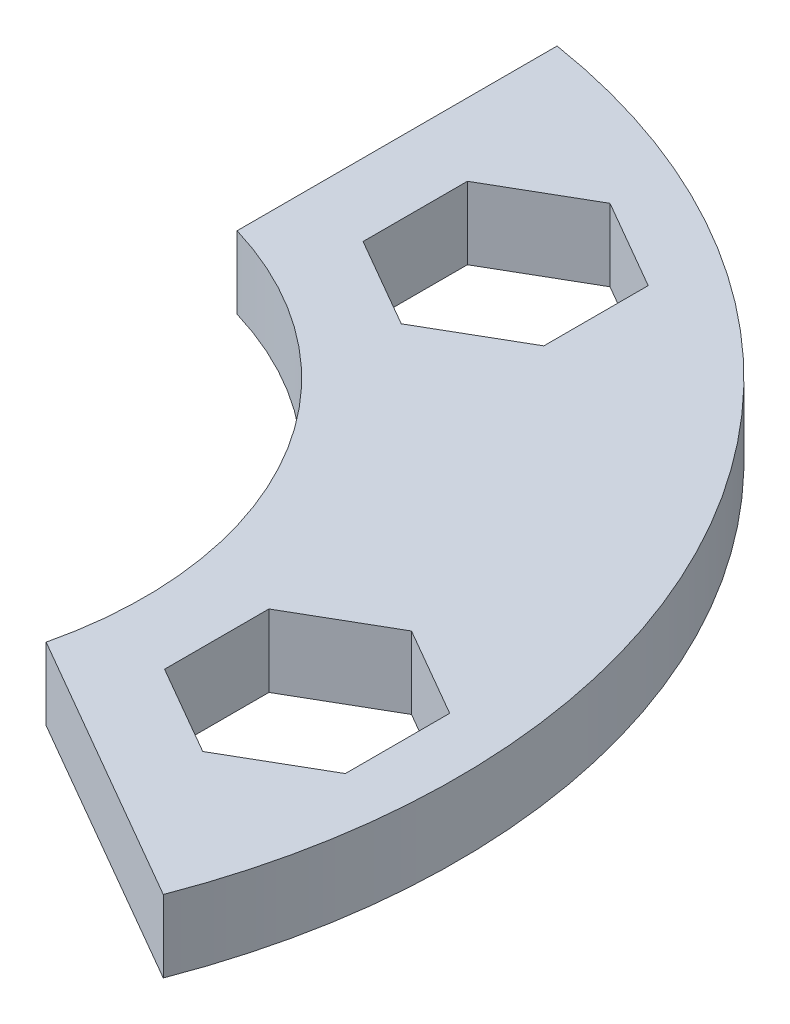
SolidWorks part; units mm, degrees
material "Balsa"
ref_plane "Front Plane" through (0, 0, 0) normal (0, 0, 1) x (1, 0, 0)
ref_plane "Top Plane" through (0, 0, 0) normal (0, 1, 0) x (1, 0, 0)
ref_plane "Right Plane" through (0, 0, 0) normal (1, 0, 0) x (0, 0, -1)
sketch "Sketch1" plane through (0, 0, 0) normal (0, 1, 0) x (1, 0, 0)
  line L0 (-38.3, 0) -> (38.3, 0) construction
  line L1 (0, 38.3) -> (0, -38.3) construction
  line L2 (10, -28.8675) -> (15, -31.7543)
  line L3 (30, 5.7735) -> (25, 2.8868)
  line L4 (25, 2.8868) -> (25, -2.8868)
  line L5 (25, -2.8868) -> (30, -5.7735)
  line L6 (30, -5.7735) -> (35, -2.8868)
  line L7 (35, -2.8868) -> (35, 2.8868)
  line L8 (35, 2.8868) -> (30, 5.7735)
  line L9 (10, -23.094) -> (10, -28.8675)
  line L10 (15, -20.2073) -> (10, -23.094)
  line L11 (20, -23.094) -> (15, -20.2073)
  line L12 (20, -28.8675) -> (20, -23.094)
  line L13 (15, -31.7543) -> (20, -28.8675)
  line L14 (-20, -23.094) -> (-20, -28.8675)
  line L15 (-15, -20.2073) -> (-20, -23.094)
  line L16 (-10, -23.094) -> (-15, -20.2073)
  line L17 (-10, -28.8675) -> (-10, -23.094)
  line L18 (-15, -31.7543) -> (-10, -28.8675)
  line L19 (-20, -28.8675) -> (-15, -31.7543)
  line L20 (-30, 5.7735) -> (-35, 2.8868)
  line L21 (-25, 2.8868) -> (-30, 5.7735)
  line L22 (-25, -2.8868) -> (-25, 2.8868)
  line L23 (-30, -5.7735) -> (-25, -2.8868)
  line L24 (-35, -2.8868) -> (-30, -5.7735)
  line L25 (-35, 2.8868) -> (-35, -2.8868)
  line L26 (-10, 28.8675) -> (-15, 31.7543)
  line L27 (-10, 23.094) -> (-10, 28.8675)
  line L28 (-15, 20.2073) -> (-10, 23.094)
  line L29 (-20, 23.094) -> (-15, 20.2073)
  line L30 (-20, 28.8675) -> (-20, 23.094)
  line L31 (-15, 31.7543) -> (-20, 28.8675)
  line L32 (20, 23.094) -> (20, 28.8675)
  line L33 (15, 20.2073) -> (20, 23.094)
  line L34 (10, 23.094) -> (15, 20.2073)
  line L35 (10, 28.8675) -> (10, 23.094)
  line L36 (15, 31.7543) -> (10, 28.8675)
  line L37 (20, 28.8675) -> (15, 31.7543)
  circle A0 centre (0, 0) radius 38.3
  circle A1 centre (30, 0) radius 5 construction
  circle A2 centre (0, 0) radius 21
  circle A3 centre (15, -25.9808) radius 5 construction
  circle A4 centre (-15, -25.9808) radius 5 construction
  circle A5 centre (-30, 0) radius 5 construction
  circle A6 centre (-15, 25.9808) radius 5 construction
  circle A7 centre (15, 25.9808) radius 5 construction
  point P23 (0, 0)
  point P60 (0, 0)
  dimension "D1" = 42
  dimension "D2" = 76.6
  dimension "D3" = 10
  dimension "D4" = 30
  dimension "D5" = 6
extrude "Boss-Extrude1" add sketch "Sketch1" along normal blind 4
sketch "Sketch2" plane through (0, 4, 0) normal (0, 1, 0) x (1, 0, 0)
  line L0 (0, 0) -> (0, 45.284) construction
  line L1 (0, 0) -> (52.3716, -30.2368) construction
  line L2 (6, 50.2763) -> (6, 14.2975)
  line L3 (15.382, -1.9526) -> (46.5406, -19.942)
  arc A0 (15.382, -1.9526) -> (6, 14.2975) centre (0, 0) ccw
  arc A2 (6, 50.2763) -> (46.5406, -19.942) centre (0, 0) ccw
  dimension "D1" = 120
  dimension "D2" = 6
  dimension "D3" = 6
extrude "Cut-Extrude1" cut sketch "Sketch2" against normal blind 10 contours L2 A0 L3 A2
